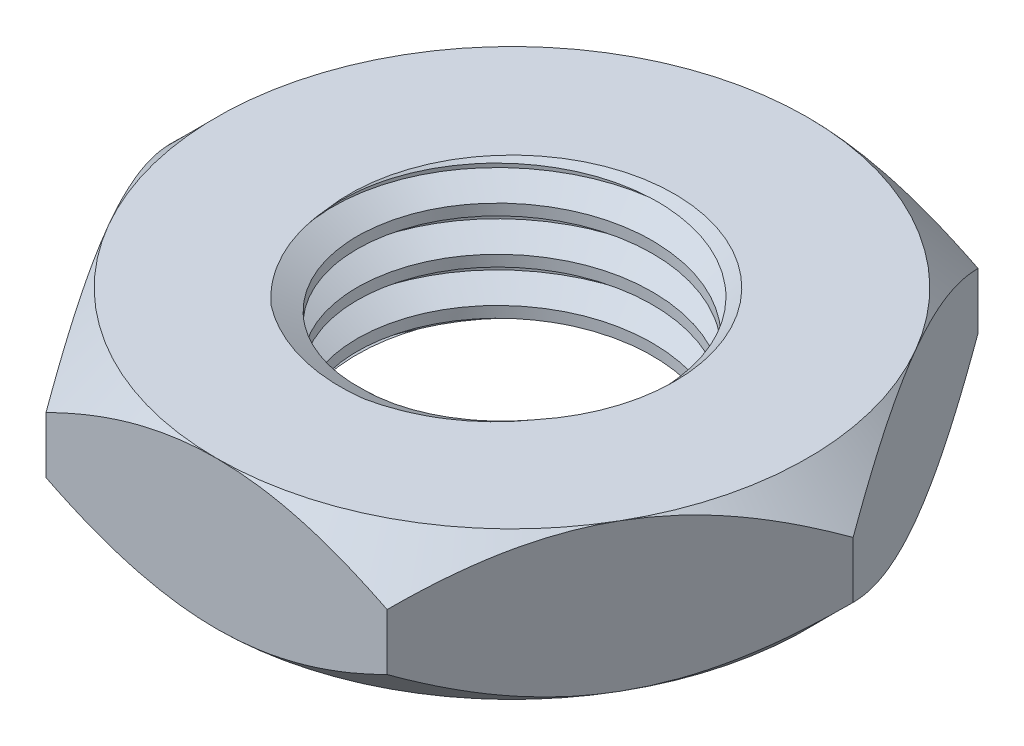
SolidWorks part; units mm, degrees
ref_plane "Front Plane" through (0, 0, 0) normal (0, 0, 1) x (1, 0, 0)
ref_plane "Top Plane" through (0, 0, 0) normal (0, 1, 0) x (1, 0, 0)
ref_plane "Right Plane" through (0, 0, 0) normal (1, 0, 0) x (0, 0, -1)
sketch "Sketch1" plane through (0, 0, 0) normal (0, 1, 0) x (1, 0, 0)
  line L1 (-5.7735, -10) -> (5.7735, -10)
  line L2 (5.7735, -10) -> (11.547, 0)
  line L3 (11.547, 0) -> (5.7735, 10)
  line L4 (5.7735, 10) -> (-5.7735, 10)
  line L5 (-5.7735, 10) -> (-11.547, 0)
  line L6 (-11.547, 0) -> (-5.7735, -10)
  circle A0 centre (0, 0) radius 10 construction
  dimension "D1" = 20
extrude "Boss-Extrude1" add sketch "Sketch1" along normal mid plane 5
sketch "Sketch2" plane through (0, 2.5, 0) normal (0, 1, 0) x (1, 0, 0)
  line L0 (-5.7735, 10) -> (-11.547, 0) construction
  circle A0 centre (0, 0) radius 10
extrude "Cut-Extrude1" cut sketch "Sketch2" against normal through all draft 45 flip side to cut
mirror "Mirror1" about plane through (0, 0, 0) normal (0, 1, 0) of "Cut-Extrude1"
sketch "Sketch3" plane through (0, 2.5, 0) normal (0, 1, 0) x (1, 0, 0)
  circle A0 centre (0, 0) radius 5
  point P3 (-2.2787, 3.7377)
  dimension "D1" = 10
extrude "Cut-Extrude2" cut sketch "Sketch3" against normal through all
chamfer "Chamfer1" distance 0.5 angle 45 1 edges at (0, 2.5, 5)
thread "Thread1" pitch 1.5 method cut profile "Thread Profile1" start angle 60, offset 2, length 0, pitch 1.5, diameter 10
ref_plane "Plane1" through (-2.5, 4, -4.3301) normal (-0.866, 0, 0.5) x (-0.5, 0, -0.866)
sketch "Thread Profile1" plane through (-2.5, 4, -4.3301) normal (-0.866, 0, 0.5) x (-0.5, 0, -0.866)
  line L0 (0, 0) -> (0, 1.5) construction
  line L1 (0, 0) -> (0.8119, 0.4687)
  line L2 (0.8119, 0.4687) -> (0.8119, 0.6562)
  line L3 (0.8119, 0.6562) -> (0, 1.125)
  line L4 (0.8119, 0.5625) -> (0, 0.5625) construction
  line L11 (0, 0) -> (0, 1.125)
  point P2 (0, 0)
  dimension "Pitch" = 1.5
  dimension "Profile_Angle" = 60
  dimension "Profile_Land" = 0.1875
  dimension "Profile_Height" = 0.8119
ref_plane "Plane2" through (-5.7735, 0.953, -10) normal (0, -1, 0) x (-1, 0, 0)
